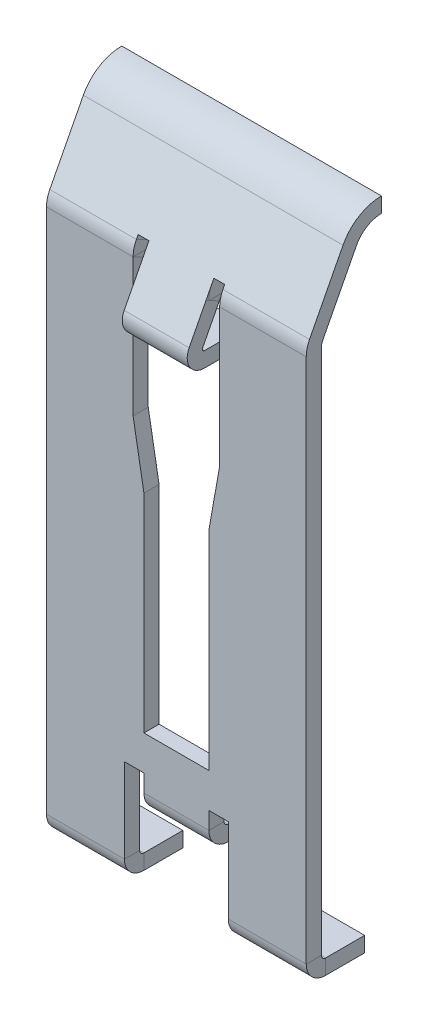
SolidWorks part; units mm, degrees
note: The reader was unsure of these and kept them because the rebuilt part matched: flange length of "Edge-Flange1".
material "AISI 1020 Steel, Cold Rolled"
ref_plane "Front" through (0, 0, 0) normal (0, 0, 1) x (1, 0, 0)
ref_plane "Top" through (0, 0, 0) normal (0, 1, 0) x (1, 0, 0)
ref_plane "Right" through (0, 0, 0) normal (1, 0, 0) x (0, 0, -1)
sketch "Sketch1" plane through (0, 0, 0) normal (0, 0, 1) x (1, 0, 0)
  line L0 (-3, 9.4) -> (-3, -2.85)
  line L1 (-3, -2.85) -> (-1.2, -2.85)
  line L2 (-1.2, -2.85) -> (-1.2, -0.8)
  line L3 (-1.2, -0.8) -> (-0.75, -0.8)
  line L4 (-0.75, -0.8) -> (-0.75, -1.3)
  line L5 (-0.75, -1.3) -> (0.75, -1.3)
  line L6 (0.75, -1.3) -> (0.75, -0.8)
  line L7 (0.75, -0.8) -> (1.2, -0.8)
  line L8 (1.2, -0.8) -> (1.2, -2.85)
  line L9 (1.2, -2.85) -> (3, -2.85)
  line L10 (3, -2.85) -> (3, 9.4)
  line L11 (-0.75, 4.8) -> (-0.75, 0)
  line L12 (-0.75, 0) -> (0.75, 0)
  line L13 (0.75, 0) -> (0.75, 4.8)
  line L14 (0, -1.3) -> (0, 0) construction
  line L15 (-3, 9.4) -> (-1, 9.4)
  line L16 (1, 9.4) -> (3, 9.4)
  line L17 (-1, 9.4) -> (-1, 6.2178)
  line L18 (-1, 6.2178) -> (-0.75, 4.8)
  line L19 (0.75, 4.8) -> (1, 6.2178)
  line L20 (1, 6.2178) -> (1, 9.4)
  dimension "D1" = 6
  dimension "D2" = 1.8
  dimension "D3" = 1.5
  dimension "D4" = 1.5
  dimension "D5" = 4.8
  dimension "D6" = 6.1
  dimension "D7" = 7.65
  dimension "D8" = 0.5
  dimension "D9" = 4.6
  dimension "D10" = 2
  dimension "D11" = 10
base flange "Main Plate" sketch "Sketch1" thickness 0.35 reverse thickness direction no parameters "D1"=1.27
edge flange "Edge-Flange1" sketch "Sketch12" flange profiles "Sketch12", "Sketch13", "Sketch14" flange angle 90 flange length 1 flange position material outside bend radius 0.1 thickness 0.35 relief rectangular parameters "D6"=10, "D8"=1
sketch "Sketch12" plane through (0, -2.85, -0.35) normal (0, -1, 0) x (-1, 0, 0)
  line L2 (-3, 0) -> (-3, 1)
  line L3 (-3, 1) -> (-1.2, 1)
  line L4 (-1.2, 1) -> (-1.2, 0)
  line L5 (-1.2, 0) -> (-3, 0) construction
  line L6 (-1.2, 0) -> (-3, 0)
sketch "Sketch13" plane through (0, -2.85, -0.35) normal (0, -1, 0) x (-1, 0, 0)
  line L0 (3, 0) -> (1.2, 0) construction
  line L1 (3, 0) -> (1.2, 0)
  line L2 (1.2, 0) -> (1.2, 1)
  line L3 (1.2, 1) -> (3, 1)
  line L4 (3, 1) -> (3, 0)
sketch "Sketch14" plane through (0, -1.3, -0.35) normal (0, -1, 0) x (-1, 0, 0)
  line L0 (0.75, 0) -> (-0.75, 0) construction
  line L1 (0.75, 0) -> (-0.75, 0)
  line L2 (-0.75, 0) -> (-0.75, 1)
  line L3 (-0.75, 1) -> (0.75, 1)
  line L4 (0.75, 1) -> (0.75, 0)
bend "EdgeBend1" bend radius 0.1 bend angle 90 parameters "D5"=1
bend "EdgeBend2" bend radius 0.1 bend angle 90 parameters "D5"=2
bend "EdgeBend3" bend radius 0.1 bend angle 90 parameters "D5"=3
sketch "Profile Sketch" plane through (0, 0, 0) normal (1, 0, 0) x (0, 0, -1)
  line L0 (-0.1, 8.1) -> (0.9, 8.1)
  line L1 (0.35, 9.4) -> (0, 9.4) construction
  line L2 (0.85, 11.2092) -> (-0.4553, 8.6837)
  line L3 (1.1609, 11.0485) -> (-0.1444, 8.523)
  line L4 (0, 13.25) -> (1.7384, 13.25)
  line L5 (-0.1, 8.45) -> (0.9, 8.45)
  line L6 (0, -2.75) -> (0, 9.4) construction
  line L7 (0.9, 8.45) -> (0.9, 8.1)
  line L8 (0.35, -2.75) -> (0.35, 9.4) construction
  line L9 (1.7384, 11.4) -> (1.7384, 11.75)
  arc A1 (-0.1, 8.1) -> (-0.4553, 8.6837) centre (-0.1, 8.5) cw
  arc A3 (-0.1, 8.45) -> (-0.1444, 8.523) centre (-0.1, 8.5) cw
  arc A4 (0, 9.4) -> (0.0756, 9.7109) centre (0.6771, 9.4) cw
  arc A5 (0.35, 9.4) -> (0.3865, 9.5502) centre (0.6771, 9.4) cw
  arc A6 (2.1631, 10.4786) -> (-0.4553, 8.6837) centre (2.5251, 7.1432) ccw construction
  arc A7 (2.2009, 10.1307) -> (-0.1444, 8.523) centre (2.5251, 7.1432) ccw construction
  arc A8 (0.85, 11.2092) -> (1.7384, 11.75) centre (1.7384, 10.75) cw
  arc A9 (1.1609, 11.0485) -> (1.7384, 11.4) centre (1.7384, 10.75) cw
  dimension "D3" = 0.4
  dimension "D6" = 0.5
  dimension "D9" = 1
  dimension "D5" = 1.5
  dimension "D1" = 1.3
  dimension "D2" = 0.5
  dimension "D4" = 5.15
  dimension "D8" = 1
  dimension "D7" = 0.35
sketch "Sketch15" plane through (0, 0, 0) normal (1, 0, 0) x (0, 0, -1)
  line L0 (0.9, 8.1) -> (0.9, 8.45)
  line L1 (0.9, 8.45) -> (-0.1, 8.45)
  line L2 (-0.1444, 8.523) -> (1.1609, 11.0485)
  line L3 (1.7384, 11.4) -> (1.7384, 11.75)
  line L4 (0.85, 11.2092) -> (-0.4553, 8.6837)
  line L5 (-0.1, 8.1) -> (0.9, 8.1)
  arc A0 (-0.1, 8.45) -> (-0.1444, 8.523) centre (-0.1, 8.5) cw
  arc A1 (1.1609, 11.0485) -> (1.7384, 11.4) centre (1.7384, 10.75) cw
  arc A2 (0.85, 11.2092) -> (1.7384, 11.75) centre (1.7384, 10.75) cw
  arc A3 (-0.4553, 8.6837) -> (-0.1, 8.1) centre (-0.1, 8.5) ccw
extrude "Central Section" add sketch "Sketch15" along normal mid plane 1.5 separate body
sketch "Sketch16" plane through (3, 0, 0) normal (1, 0, 0) x (0, 0, -1)
  line L0 (0.35, 9.4) -> (0, 9.4)
  line L1 (0.0756, 9.7109) -> (0.85, 11.2092)
  line L2 (1.7384, 11.75) -> (1.7384, 11.4)
  line L3 (1.1609, 11.0485) -> (0.3865, 9.5502)
  arc A0 (0, 9.4) -> (0.0756, 9.7109) centre (0.6771, 9.4) cw
  arc A1 (0.85, 11.2092) -> (1.7384, 11.75) centre (1.7384, 10.75) cw
  arc A2 (1.7384, 11.4) -> (1.1609, 11.0485) centre (1.7384, 10.75) ccw
  arc A3 (0.3865, 9.5502) -> (0.35, 9.4) centre (0.6771, 9.4) ccw
extrude "Boss-Extrude3" add sketch "Sketch16" along direction (-1, 0, 0) on the side against the normal up to surface (2.25 mm away) up to face at (0.75, 9.5807, -0.6178)
sketch "Sketch19" plane through (-3, 0, 0) normal (-1, 0, 0) x (0, 0, 1)
  line L0 (-0.35, 9.4) -> (0, 9.4)
  line L1 (-0.0756, 9.7109) -> (-0.85, 11.2092)
  line L2 (-1.7384, 11.75) -> (-1.7384, 11.4)
  line L3 (-1.1609, 11.0485) -> (-0.3865, 9.5502)
  arc A0 (0, 9.4) -> (-0.0756, 9.7109) centre (-0.6771, 9.4) ccw
  arc A1 (-0.85, 11.2092) -> (-1.7384, 11.75) centre (-1.7384, 10.75) ccw
  arc A2 (-1.7384, 11.4) -> (-1.1609, 11.0485) centre (-1.7384, 10.75) cw
  arc A3 (-0.3865, 9.5502) -> (-0.35, 9.4) centre (-0.6771, 9.4) cw
extrude "Boss-Extrude4" add sketch "Sketch19" against normal up to surface (2.25 mm away) up to face at (-0.75, 9.5807, -0.6178)
sketch "Sketch20" plane through (0, 2.0165, 3.9014) normal (0, 0.4592, 0.8884) x (1, 0, 0)
  line L0 (0, 0) -> (0, 11.2363) construction
  line L1 (0.75, 8.3505) -> (1, 8.3505)
  line L2 (0.75, 8.3505) -> (0.75, 8.7505)
  line L3 (0.75, 8.7505) -> (1, 8.7505)
  line L4 (1, 8.3505) -> (1, 8.7505)
  line L5 (-0.75, 8.3505) -> (-1, 8.3505)
  line L6 (-0.75, 8.3505) -> (-0.75, 8.7505)
  line L7 (-0.75, 8.7505) -> (-1, 8.7505)
  line L8 (-1, 8.3505) -> (-1, 8.7505)
  line L9 (-3, 11.2363) -> (3, 11.2363) construction
  line L10 (-1, 5.5236) -> (-1, 8.3505) construction
  dimension "D1" = 0.4
extrude "Cut-Extrude1" cut sketch "Sketch20" against normal blind 1 normal cut yes
sketch "Bend-Lines1" plane through (0, 0, 0) normal (0, 1, 0) x (1, 0, 0)
sketch "Bounding-Box1" plane through (0, 0, 0) normal (0, 1, 0) x (1, 0, 0)
sheet metal parameters "Sheet-Metal(1)" thickness 0.35 parameters "D1"=1.27
flat pattern "Flat-Pattern(1)" [suppressed]
sketch "Bend-Lines2" plane through (0, 0, 0) normal (0, 1, 0) x (1, 0, 0)
sketch "Bounding-Box2" [suppressed] plane through (0, 0, 0) normal (0, 1, 0) x (1, 0, 0)
sheet metal parameters "Sheet-Metal(2)" thickness 0.35 parameters "D1"=1.27
flat pattern "Flat-Pattern(1)" [suppressed]
sketch "Bend-Lines2" plane through (0, 0, 0) normal (0, 1, 0) x (1, 0, 0)
sketch "Bounding-Box2" [suppressed] plane through (0, 0, 0) normal (0, 1, 0) x (1, 0, 0)
bend of the flat pattern "Flatten-<EdgeBend1>1"
bend of the flat pattern "Flatten-<EdgeBend2>1"
bend of the flat pattern "Flatten-<EdgeBend3>1"
sheet metal parameters "Sheet-Metal(5)" thickness 0.35 parameters "D1"=1.27
flat pattern "Flat-Pattern(5)" [suppressed]
sketch "Bend-Lines3" plane through (0, 0, 0) normal (0, 1, 0) x (1, 0, 0)
sketch "Bounding-Box3" [suppressed] plane through (0, 0, 0) normal (0, 1, 0) x (1, 0, 0)
bend of the flat pattern "Flatten-<EdgeBend1>2"
bend of the flat pattern "Flatten-<EdgeBend2>2"
bend of the flat pattern "Flatten-<EdgeBend3>2"
sheet metal parameters "Sheet-Metal(6)" thickness 0.35 parameters "D1"=1.27
flat pattern "Flat-Pattern(5)" [suppressed]
sketch "Bend-Lines3" plane through (0, 0, 0) normal (0, 1, 0) x (1, 0, 0)
sketch "Bounding-Box3" [suppressed] plane through (0, 0, 0) normal (0, 1, 0) x (1, 0, 0)
bend of the flat pattern "Flatten-<EdgeBend1>2"
bend of the flat pattern "Flatten-<EdgeBend2>2"
bend of the flat pattern "Flatten-<EdgeBend3>2"
sheet metal parameters "Sheet-Metal(7)" thickness 0.35 parameters "D1"=1.27
flat pattern "Flat-Pattern(5)" [suppressed]
sketch "Bend-Lines3" plane through (0, 0, 0) normal (0, 1, 0) x (1, 0, 0)
sketch "Bounding-Box3" [suppressed] plane through (0, 0, 0) normal (0, 1, 0) x (1, 0, 0)
bend of the flat pattern "Flatten-<EdgeBend1>2"
bend of the flat pattern "Flatten-<EdgeBend2>2"
bend of the flat pattern "Flatten-<EdgeBend3>2"
